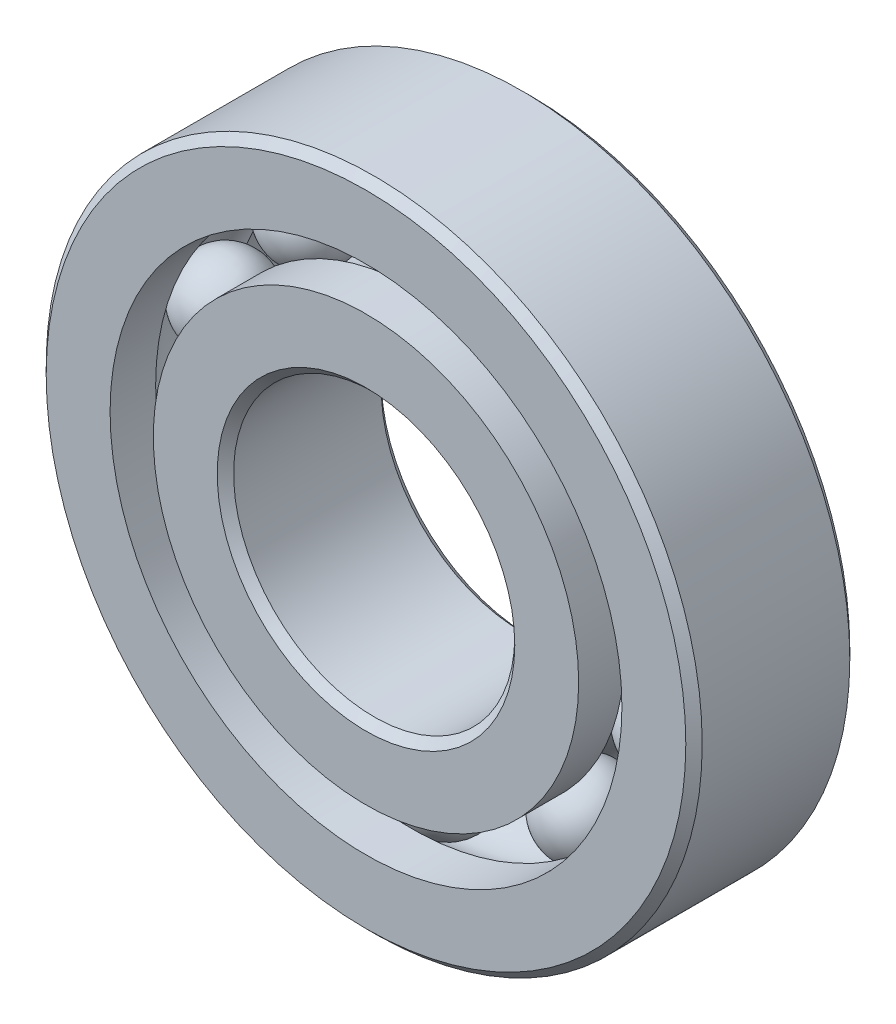
SolidWorks part; units mm, degrees
ref_plane "Front Plane" through (0, 0, 0) normal (0, 0, 1) x (1, 0, 0)
ref_plane "Top Plane" through (0, 0, 0) normal (0, 1, 0) x (1, 0, 0)
ref_plane "Right Plane" through (0, 0, 0) normal (1, 0, 0) x (0, 0, -1)
sketch "Sketch1" plane through (0, 0, 0) normal (1, 0, 0) x (0, 0, -1)
  line L0 (-2.7781, 0) -> (2.7781, 0) construction
  line L1 (0, 11.1125) -> (0, -11.1125) construction
  line L2 (2.5003, 11.1125) -> (-2.5003, 11.1125)
  line L3 (-2.5003, 11.1125) -> (-2.7781, 10.8347)
  line L4 (-2.7781, 10.8347) -> (-2.7781, 8.6702)
  line L5 (-2.7781, 8.6702) -> (-1.2347, 8.6702)
  line L6 (2.7781, 8.6702) -> (1.2347, 8.6702)
  line L7 (2.7781, 10.8347) -> (2.7781, 8.6702)
  line L8 (2.5003, 11.1125) -> (2.7781, 10.8347)
  line L9 (0, 11.1125) -> (0, 7.9375) construction
  line L10 (0, 7.9375) -> (0, 4.7625) construction
  arc A0 (-1.2347, 8.6702) -> (1.2347, 8.6702) centre (0, 7.9375) cw
  point P14 (0, 4.7625)
  dimension "Width" = 5.5562
  dimension "OD" = 22.225
  dimension "D1" = 45
  dimension "D2" = 0.2778
  dimension "Shaft Dia" = 9.525
  dimension "D3" = 2.4694
  dimension "D4" = 0.7327
revolve "Revolve1" add sketch "Sketch1" angle 360 about L0
sketch "Sketch3" plane through (0, 0, 0) normal (1, 0, 0) x (0, 0, -1)
  line L0 (-2.7781, 7.2048) -> (-1.2347, 7.2048)
  line L1 (0, 11.1125) -> (0, -11.1125) construction
  line L2 (-2.7781, 10.8347) -> (-2.7781, 8.6702) construction
  line L3 (-2.7781, 7.2048) -> (-2.7781, 5.0403)
  line L4 (-2.5003, 11.1125) -> (-2.7781, 10.8347) construction
  line L5 (-2.7781, 5.0403) -> (-2.5003, 4.7625)
  line L6 (-2.5003, 4.7625) -> (2.5003, 4.7625)
  line L7 (2.5003, 11.1125) -> (2.5003, -11.1125) construction
  line L8 (2.5003, 4.7625) -> (2.7781, 5.0403)
  line L9 (2.7781, -10.8347) -> (2.7781, 10.8347) construction
  line L10 (2.7781, 5.0403) -> (2.7781, 7.2048)
  line L11 (2.7781, 7.2048) -> (1.2347, 7.2048)
  line L13 (2.5003, 11.1125) -> (2.7781, 10.8347) construction
  arc A0 (1.2347, 8.6702) -> (-1.2347, 8.6702) centre (0, 7.9375) ccw construction
  arc A1 (1.2347, 7.2048) -> (-1.2347, 7.2048) centre (0, 7.9375) cw
revolve "Revolve3" add sketch "Sketch3" angle 360 about L0
sketch "Sketch4" plane through (0, 0, 0) normal (1, 0, 0) x (0, 0, -1)
  line L0 (-1.4357, 7.9375) -> (1.4357, 7.9375)
  arc A2 (-1.4357, 7.9375) -> (1.4357, 7.9375) centre (0, 7.9375) cw
  arc A3 (1.2347, 8.6702) -> (-1.2347, 8.6702) centre (0, 7.9375) ccw construction
revolve "Revolve4" add sketch "Sketch4" angle 360 about L0
ref_axis "Axis1" through (0, 0, -2.7781) along (0, 0, 1)
pattern_circular "CirPattern1" count 10 every 36 about axis through (0, 0, -2.7781) along (0, 0, 1) of bodies 104
sketch "Sketch5" plane through (0, 0, 0) normal (1, 0, 0) x (0, 0, -1)
  line L0 (-2.7781, 8.6702) -> (-1.2347, 8.6702) construction
  line L1 (-2.6392, 8.6702) -> (-1.4357, 8.6702)
  line L2 (-2.6392, 8.6702) -> (-2.6392, 7.2048)
  line L3 (-2.6392, 7.2048) -> (-1.4357, 7.2048)
  line L4 (-1.4357, 8.6702) -> (-1.4357, 7.2048)
  line L5 (-2.7781, 7.2048) -> (-1.2347, 7.2048) construction
  line L6 (2.7781, 8.6702) -> (1.2347, 8.6702) construction
  line L7 (2.6392, 8.6702) -> (1.4357, 8.6702)
  line L8 (2.6392, 8.6702) -> (2.6392, 7.2048)
  line L9 (2.6392, 7.2048) -> (1.4357, 7.2048)
  line L10 (1.4357, 8.6702) -> (1.4357, 7.2048)
  line L11 (2.7781, 7.2048) -> (1.2347, 7.2048) construction
  line L12 (-2.5003, 11.1125) -> (-2.7781, 10.8347) construction
  point P18 (-2.6392, 10.9736)
revolve "Revolve5" [suppressed] add sketch "Sketch5" angle 360 about L0
ref_axis "Axis2" through (0, 0, -2.5003) along (0, 0, 1)
equation "\"D2@Sketch1\" = \"Width@Sketch1\"*.05"
equation "\"D3@Sketch1\" = \"Width@Sketch1\"/2.25"
equation "\"D4@Sketch1\" = (((\"OD@Sketch1\"-\"Width@Sketch1\")/2)/3.25)/3.5"
equation "\"D2@CirPattern1\" = 360/\"Balls@CirPattern1\""
